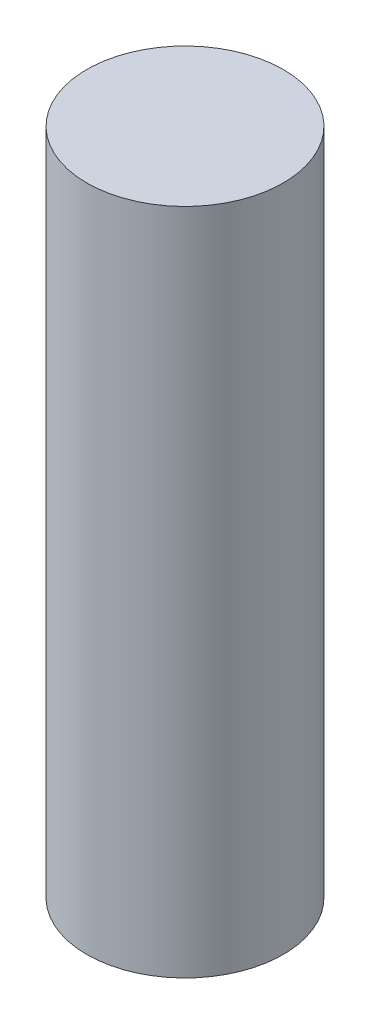
SolidWorks part; units mm, degrees
material "1023 Carbon Steel Sheet (SS)"
ref_plane "Front Plane" through (0, 0, 0) normal (0, 0, 1) x (1, 0, 0)
ref_plane "Top Plane" through (0, 0, 0) normal (0, 1, 0) x (1, 0, 0)
ref_plane "Right Plane" through (0, 0, 0) normal (1, 0, 0) x (0, 0, -1)
sketch "Sketch1" plane through (0, 0, 0) normal (0, 1, 0) x (1, 0, 0)
  circle A0 centre (0, 0) radius 3
  dimension "D1" = 6
extrude "Boss-Extrude1" add sketch "Sketch1" along normal blind 20.3962 contours A0
